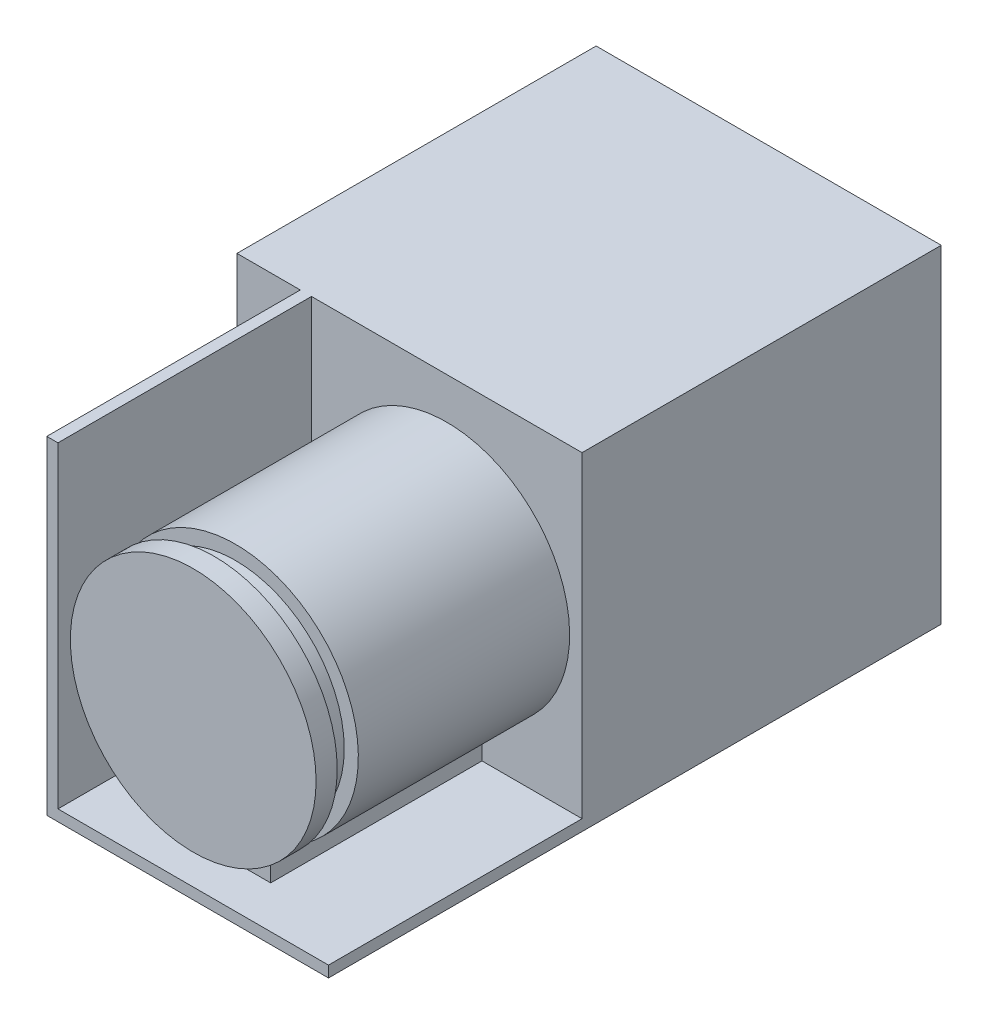
SolidWorks part; units mm, degrees
ref_plane "Front Plane" through (0, 0, 0) normal (0, 0, 1) x (1, 0, 0)
ref_plane "Top Plane" through (0, 0, 0) normal (0, 1, 0) x (1, 0, 0)
ref_plane "Right Plane" through (0, 0, 0) normal (1, 0, 0) x (0, 0, -1)
sketch "Sketch1" plane through (0, 0, 0) normal (0, 0, 1) x (1, 0, 0)
  line L1 (24.5, 23.3) -> (-24.5, 23.3)
  line L2 (24.5, 23.3) -> (24.5, -23.3)
  line L3 (24.5, -23.3) -> (-24.5, -23.3)
  line L4 (-24.5, 23.3) -> (-24.5, -23.3)
  line L5 (24.5, 23.3) -> (-24.5, -23.3) construction
  line L6 (24.5, -23.3) -> (-24.5, 23.3) construction
  point P0 (0, 0)
  dimension "D1" = 49
  dimension "D2" = 46.6
extrude "Boss-Extrude1" add sketch "Sketch1" along normal blind 51
sketch "Sketch2" plane through (0, 0, 51) normal (0, 0, 1) x (1, 0, 0)
  line L0 (24.5, -23.3) -> (24.5, -21.7125)
  line L1 (24.5, -23.3) -> (24.5, 23.3) construction
  line L2 (24.5, -21.7125) -> (-13.9125, -21.7125)
  line L3 (-13.9125, -21.7125) -> (-13.9125, 23.3)
  line L4 (24.5, 23.3) -> (-24.5, 23.3) construction
  line L5 (-13.9125, 23.3) -> (-15.5, 23.3)
  line L6 (-15.5, 23.3) -> (-15.5, -23.3)
  line L7 (-24.5, -23.3) -> (24.5, -23.3) construction
  line L8 (-15.5, -23.3) -> (24.5, -23.3)
  dimension "D1" = 40
  dimension "D2" = 1.5875
extrude "Boss-Extrude2" add sketch "Sketch2" along normal blind 36
sketch "Sketch3" plane through (0, 0, 51) normal (0, 0, 1) x (1, 0, 0)
  line L0 (0.2937, -21.7125) -> (0.2937, -16.7125)
  line L1 (24.5, -21.7125) -> (-13.9125, -21.7125) construction
  line L2 (0.2937, -21.7125) -> (10.2938, -21.7125)
  line L3 (24.5, -21.7125) -> (-13.9125, -21.7125) construction
  line L4 (10.2938, -21.7125) -> (10.2938, -16.7125)
  arc A0 (10.2938, -16.7125) -> (0.2937, -16.7125) centre (5.2938, 0) ccw
  point P6 (5.2938, -21.7125)
  dimension "D1" = 10
  dimension "D2" = 5
extrude "Boss-Extrude3" add sketch "Sketch3" along normal up to surface (36 mm away) up to face at (-1.6375, -7.2375, 87)
sketch "Sketch4" plane through (0, 0, 87) normal (0, 0, 1) x (1, 0, 0)
  circle A3 centre (5.2938, 0) radius 15.4444
  circle A4 centre (5.2938, 0) radius 17.4444
  arc A5 (10.2937, -16.7125) -> (0.2937, -16.7125) centre (5.2938, 0) ccw construction
  dimension "D1" = 2
extrude "Cut-Extrude1" cut sketch "Sketch4" against normal blind 3 from offset 3 offset against normal yes
sketch "Sketch5" plane through (0, 0, 87) normal (0, 0, 1) x (1, 0, 0)
  line L1 (0.2937, -21.7125) -> (10.2937, -21.7125)
  line L2 (0.2937, -21.7125) -> (0.2937, -16.7125)
  line L4 (10.2937, -21.7125) -> (10.2937, -16.7125)
  arc A0 (0.2937, -16.7125) -> (10.2937, -16.7125) centre (5.2938, 0) ccw
extrude "Cut-Extrude2" cut sketch "Sketch5" against normal up to surface (6 mm away) up to face at (20.7382, 0, 81)
